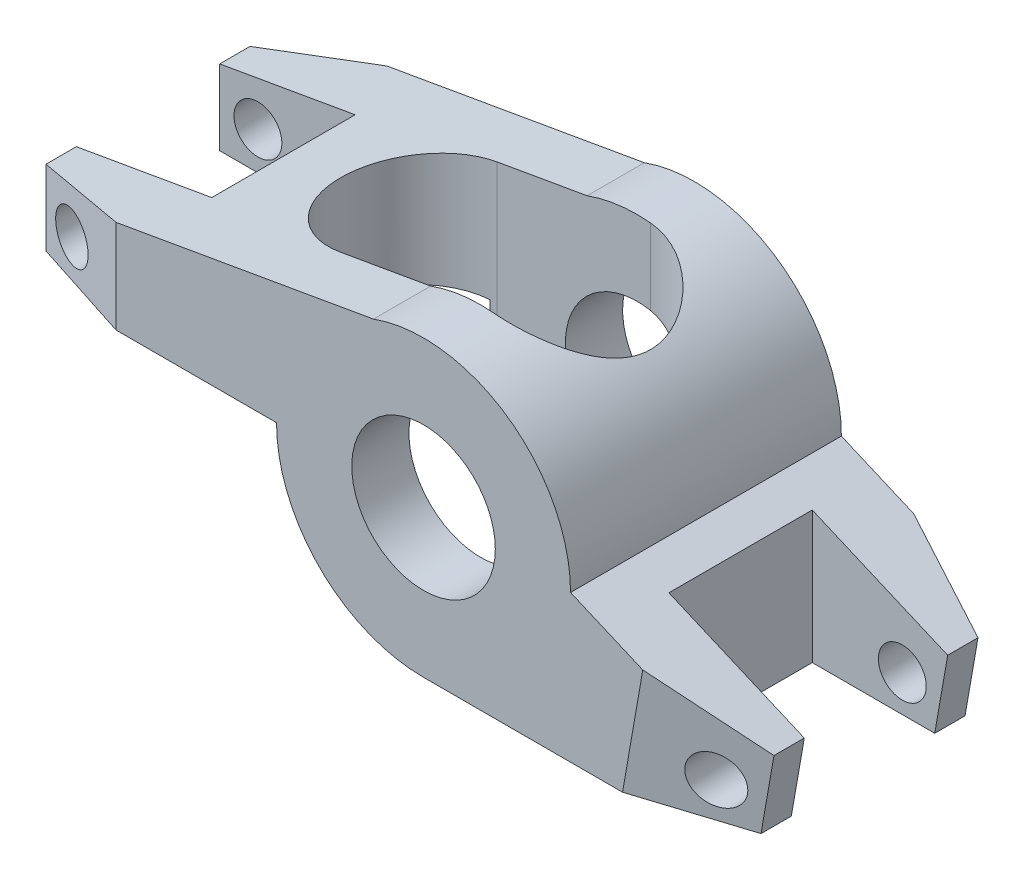
SolidWorks part; units mm, degrees
ref_plane "Front Plane" through (0, 0, 0) normal (0, 0, 1) x (1, 0, 0)
ref_plane "Top Plane" through (0, 0, 0) normal (0, 1, 0) x (1, 0, 0)
ref_plane "Right Plane" through (0, 0, 0) normal (1, 0, 0) x (0, 0, -1)
sketch "Sketch1" plane through (0, 0, 0) normal (0, 0, 1) x (1, 0, 0)
  line L0 (-27.31, 0) -> (-27.31, 5)
  line L1 (-3.329, 9.1854) -> (-27.31, 5)
  line L2 (-27.31, 0) -> (-9.77, 0)
  line L3 (21.07, -4.8445) -> (20.2104, -9.77)
  line L4 (9.77, 0) -> (21.07, -4.8445)
  line L5 (20.2104, -9.77) -> (0, -9.77)
  line L7 (4, 0) -> (4, -25.7441) construction
  circle A0 centre (0, 0) radius 4.77
  arc A1 (-9.77, 0) -> (0, -9.77) centre (0, 0) ccw
  circle A2 centre (-24.77, 2.5) radius 1.59
  arc A3 (9.77, 0) -> (-3.329, 9.1854) centre (0, 0) ccw
  circle A4 centre (18.0553, -7.3445) radius 1.59
  dimension "D1" = 9.54
  dimension "D2" = 19.54
  dimension "D7" = 3.18
  dimension "D10" = 80.1
  dimension "D12" = 3.18
  dimension "D3" = 27.31
  dimension "D4" = 5
  dimension "D5" = 21.07
  dimension "D6" = 5
  dimension "D8" = 9.9
  dimension "D9" = 2.54
  dimension "D11" = 2.5
  dimension "D13" = 2.54
  dimension "D14" = 2.5
extrude "Boss-Extrude1" add sketch "Sketch1" along normal blind 18
chamfer "Chamfer1" distance 6.88 distance2 2.22 2 edges at (-27.31, 2.5, 0) (-27.31, 2.5, 18) first distance on face at (-2.0379, -1.102, 0) first distance on face at (-23.18, 2.5, 18)
chamfer "Chamfer2" distance 2.22 distance2 6.88 2 edges at (20.6402, -7.3072, 0) (20.6402, -7.3072, 18) first distance on face at (20.6402, -7.3072, 9)
sketch "Sketch3" plane through (0, 0, 0) normal (0, 1, 0) x (1, 0, 0)
  line L0 (-27.31, -9) -> (22.5335, -9) construction
  line L1 (-27.31, -15.78) -> (-27.31, -2.22) construction
  line L2 (-9.31, -9) -> (0.89, -9) construction
  line L3 (-27.31, -4.235) -> (-18.31, -4.235)
  line L4 (-27.31, -4.235) -> (-27.31, -13.765)
  line L5 (-27.31, -13.765) -> (-18.31, -13.765)
  line L6 (-18.31, -4.235) -> (-18.31, -13.765)
  line L7 (-9.31, -3.8) -> (0.89, -3.8)
  line L8 (-9.31, -14.2) -> (0.89, -14.2)
  line L14 (-3.12, 5.4185) -> (-3.12, -24.2745) construction
  line L15 (12.07, -4.235) -> (12.07, -13.765)
  line L16 (21.07, -13.765) -> (12.07, -13.765)
  line L17 (21.07, -4.235) -> (21.07, -13.765)
  line L18 (21.07, -4.235) -> (12.07, -4.235)
  line L19 (21.07, -15.78) -> (21.07, -2.22) construction
  arc A0 (-9.31, -3.8) -> (-9.31, -14.2) centre (-9.31, -9) ccw
  arc A1 (0.89, -14.2) -> (0.89, -3.8) centre (0.89, -9) ccw
  point P10 (-4.21, -9)
  dimension "D4" = 5.2
  dimension "D5" = 9
  dimension "D1" = 9.53
  dimension "D2" = 9
  dimension "D3" = 10.2
extrude "Cut-Extrude1" cut sketch "Sketch3" against normal through all both and the other way through all
